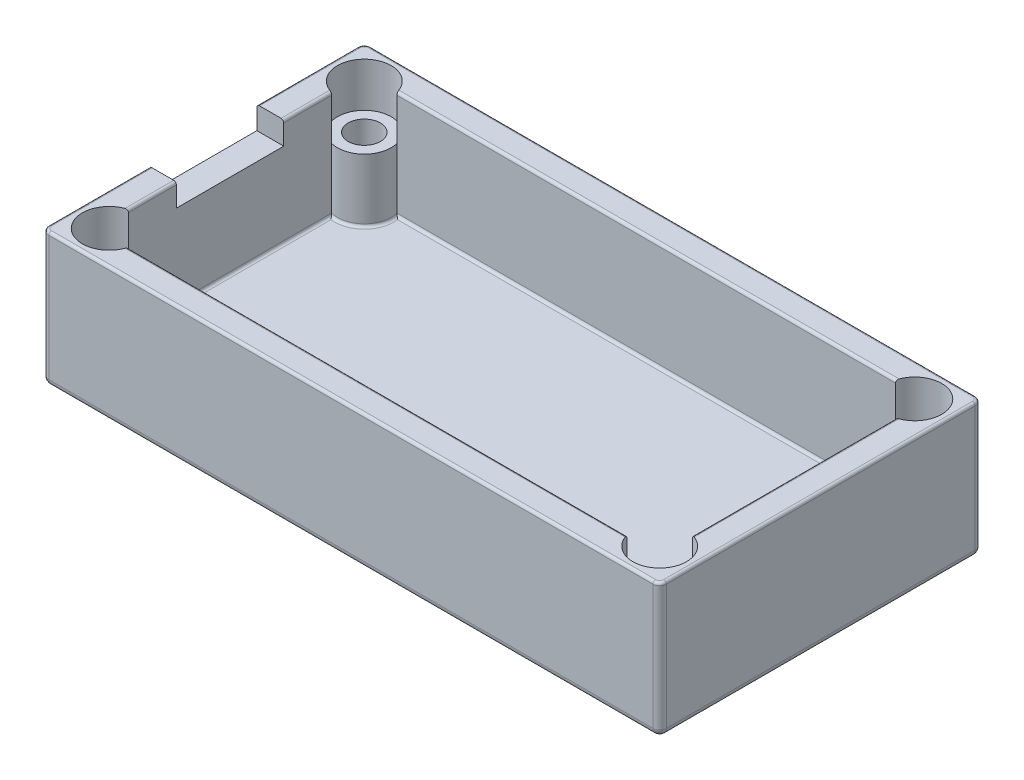
SolidWorks part; units mm, degrees
ref_plane "前视基准面" through (0, 0, 0) normal (0, 0, 1) x (1, 0, 0)
ref_plane "上视基准面" through (0, 0, 0) normal (0, 1, 0) x (1, 0, 0)
ref_plane "右视基准面" through (0, 0, 0) normal (1, 0, 0) x (0, 0, -1)
sketch "草图1" plane through (0, 0, 0) normal (0, 1, 0) x (1, 0, 0)
  line L0 (0, 0) -> (0, 9.4466) construction
  line L1 (-11.5, 6) -> (11.5, 6)
  line L2 (-11.5, 6) -> (-11.5, -6)
  line L3 (-11.5, -6) -> (11.5, -6)
  line L4 (11.5, 6) -> (11.5, -6)
  line L5 (-11.5, 6) -> (11.5, -6) construction
  line L6 (-11.5, -6) -> (11.5, 6) construction
  circle A0 centre (-10.25, -4.75) radius 1
  circle A1 centre (-10.25, 4.75) radius 1
  circle A2 centre (10.25, -4.75) radius 1
  circle A3 centre (10.25, 4.75) radius 1
  point P0 (0, 0)
  dimension "D3" = 2
  dimension "D5" = 1.25
  dimension "D1" = 12
  dimension "D2" = 23
  dimension "D4" = 1.25
  dimension "D6" = 1.25
  dimension "D7" = 1.25
extrude "凸台-拉伸1" add sketch "草图1" along normal blind 5 contours L3 L4 L1 L2
shell "抽壳1" thickness 1 removed face at (0, 5, 0)
fillet "圆角1" radius 0.25 8 edges at (0, 0, 6) (11.5, 0, 0) (0, 0, -6) (-11.5, 0, 0) (11.5, 2.5, 6) (11.5, 2.5, -6) (-11.5, 2.5, -6) (-11.5, 2.5, 6)
fillet "圆角2" radius 0.1 12 edges at (-11.4268, 5, 5.9268) (-11.5, 5, 0) (-11.4268, 5, -5.9268) (0, 5, -6) (11.4268, 5, -5.9268) (11.5, 5, 0) (11.4268, 5, 5.9268) (0, 5, 6) (0, 5, 5) (10.5, 5, 0) (0, 5, -5) (-10.5, 5, 0)
extrude "切除-拉伸1" cut sketch "草图1<3>" along normal through all contours A1 | A2 | A3 | A0 region at (-10.25, 0, -4.75)
sketch "草图1<3>" plane through (0, 0, 0) normal (0, 1, 0) x (1, 0, 0) same geometry as "草图1"
extrude "拉伸-薄壁1" add sketch "草图1<4>" along normal blind 2.5 from offset 0.85 thin contours A2 | A3 | A0 | A1 thin type one direction reverse wall 0.4
sketch "草图1<4>" plane through (0, 0, 0) normal (0, 1, 0) x (1, 0, 0) same geometry as "草图1"
sketch "草图3" plane through (-11.5, 0, 0) normal (-1, 0, 0) x (0, 0, 1)
  line L0 (5.75, 4.9) -> (-5.75, 4.9) construction
  line L1 (-2, 5.65) -> (2, 5.65)
  line L2 (-2, 5.65) -> (-2, 4.15)
  line L3 (-2, 4.15) -> (2, 4.15)
  line L4 (2, 5.65) -> (2, 4.15)
  line L5 (-2, 5.65) -> (2, 4.15) construction
  line L6 (-2, 4.15) -> (2, 5.65) construction
  point P0 (0, 4.9)
  dimension "D1" = 4
  dimension "D2" = 1.5
extrude "切除-拉伸2" cut sketch "草图3" against normal blind 2.5
fillet "圆角3" radius 0.1 8 edges at (-9.5429, 1, -4.0429) (0, 1, -5) (9.5429, 1, -4.0429) (10.5, 1, 0) (9.5429, 1, 4.0429) (0, 1, 5) (-9.5429, 1, 4.0429) (-10.5, 1, 0)
